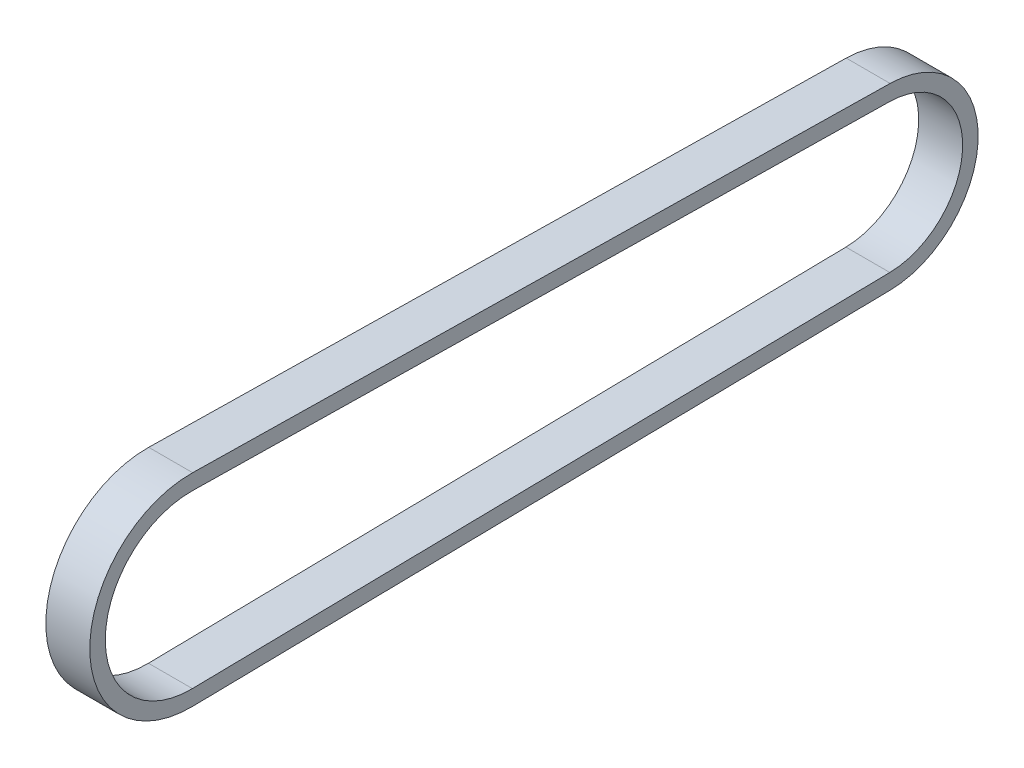
SolidWorks part; units mm, degrees
ref_plane "Front Plane" through (0, 0, 0) normal (0, 0, 1) x (1, 0, 0)
ref_plane "Top Plane" through (0, 0, 0) normal (0, 1, 0) x (1, 0, 0)
ref_plane "Right Plane" through (0, 0, 0) normal (1, 0, 0) x (0, 0, -1)
other "Bounding Box"
ref_plane "Default Plane" through (-8.9266, -12.7485, 0) normal (-0.1736, 0.9848, 0) x (0.9848, 0.1736, 0)
sketch "Sketch1" plane through (0, 0, 0) normal (1, 0, 0) x (0, 0, -1)
  line L0 (0, 0) -> (142.875, 0) construction
  line L1 (0.2929, 17.5464) -> (143.1281, 15.1617)
  line L2 (0.2929, -17.5464) -> (143.1281, -15.1617)
  line L3 (0.346, 20.721) -> (143.1811, 18.3362)
  line L4 (0.346, -20.721) -> (143.1811, -18.3362)
  line L5 (-17.5489, 0) -> (-20.7239, 0) construction
  line L6 (158.0388, 0) -> (161.2138, 0) construction
  arc A0 (0.2929, 17.5464) -> (0.2929, -17.5464) centre (0, 0) ccw
  arc A1 (143.1281, -15.1617) -> (143.1281, 15.1617) centre (142.875, 0) ccw
  arc A2 (0.346, 20.721) -> (0.346, -20.721) centre (0, 0) ccw
  arc A3 (143.1811, -18.3362) -> (143.1811, 18.3362) centre (142.875, 0) ccw
  dimension "D2" = 3.175
  dimension "D3" = 15.1638
  dimension "D4" = 35.0977
  dimension "D1" = 142.875
extrude "Boss-Extrude1" add sketch "Sketch1" along normal mid plane 9
